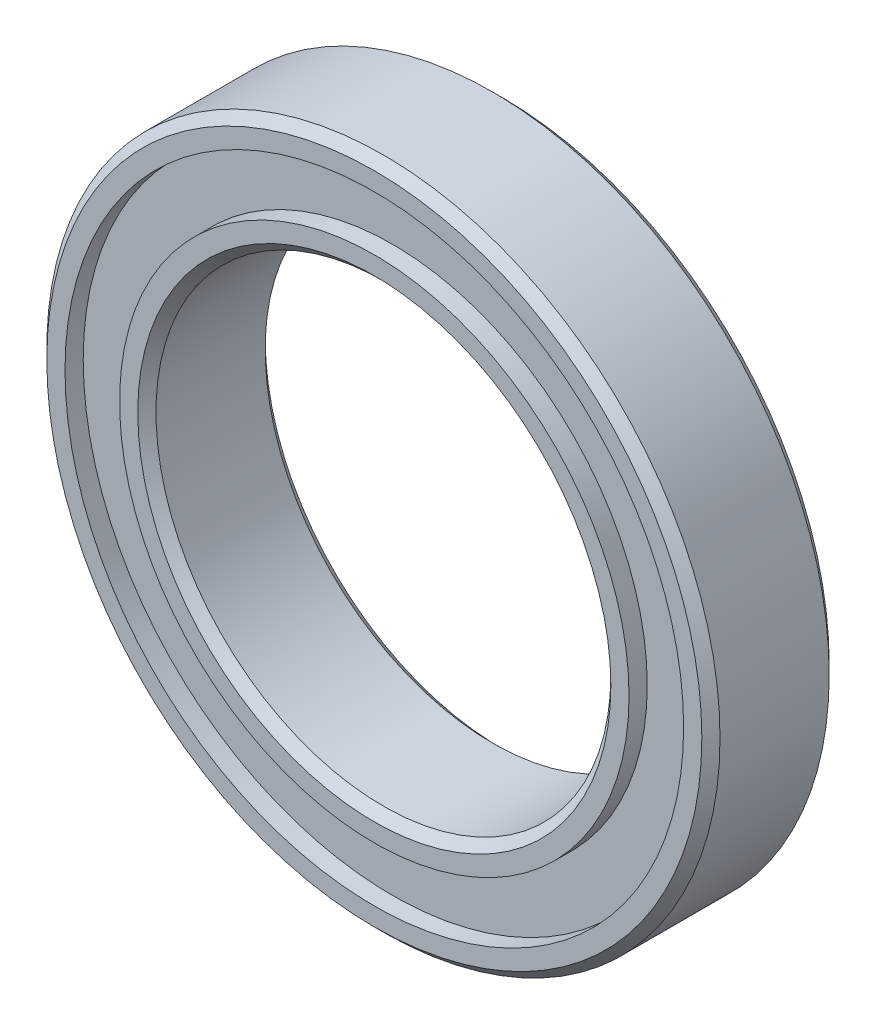
SolidWorks part; units mm, degrees
ref_plane "Ebene vorne" through (0, 0, 0) normal (0, 0, 1) x (1, 0, 0)
ref_plane "Ebene oben" through (0, 0, 0) normal (0, 1, 0) x (1, 0, 0)
ref_plane "Ebene rechts" through (0, 0, 0) normal (1, 0, 0) x (0, 0, -1)
sketch "Skizze1" plane through (0, 0, 0) normal (0, 0, 1) x (1, 0, 0)
  circle A0 centre (0, 0) radius 12.5
  circle A1 centre (0, 0) radius 18.5
  dimension "D1" = 25
  dimension "D2" = 37
extrude "Aufsatz-Linear austragen1" add sketch "Skizze1" along normal blind 3.5 and the other way blind 3.5
sketch "Skizze2" plane through (0, 0, 3.5) normal (0, 0, 1) x (1, 0, 0)
  circle A0 centre (0, 0) radius 14
  circle A1 centre (0, 0) radius 17
  dimension "D1" = 28
  dimension "D2" = 34
extrude "Schnitt-Linear austragen1" cut sketch "Skizze2" against normal blind 1
mirror "Spiegeln1" about plane through (0, 0, 0) normal (0, 0, 1) of "Schnitt-Linear austragen1"
chamfer "Fase1" distance 0.5 angle 45 4 edges at (12.5, 0, 3.5) (12.5, 0, -3.5) (18.5, 0, 3.5) (18.5, 0, -3.5)
